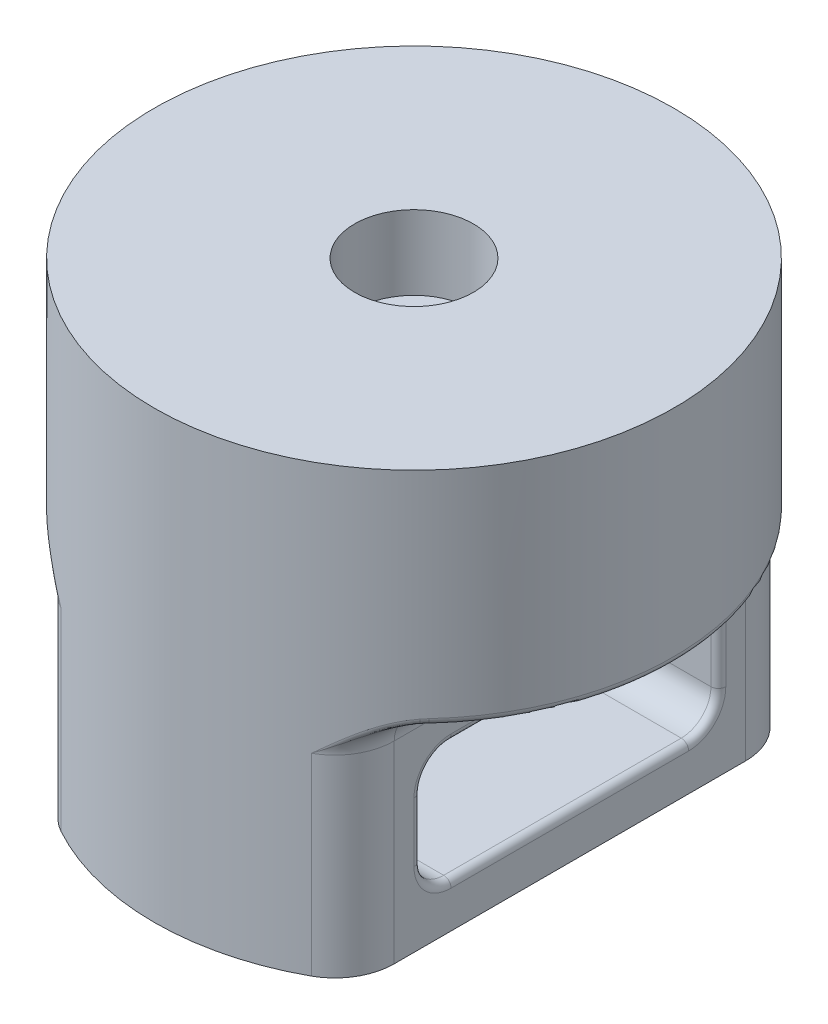
SolidWorks part; units mm, degrees
ref_plane "Front Plane" through (0, 0, 0) normal (0, 0, 1) x (1, 0, 0)
ref_plane "Top Plane" through (0, 0, 0) normal (0, 1, 0) x (1, 0, 0)
ref_plane "Right Plane" through (0, 0, 0) normal (1, 0, 0) x (0, 0, -1)
sketch "Sketch1" plane through (0, 0, 0) normal (0, 1, 0) x (1, 0, 0)
  circle A0 centre (0, 0) radius 17.5
  dimension "D1" = 35
extrude "Boss-Extrude1" add sketch "Sketch1" against normal blind 30
sketch "Sketch2" plane through (0, 0, 0) normal (0, 0, 1) x (1, 0, 0)
  line L0 (-17.5, -15) -> (-10.5, -15)
  line L1 (0, 0) -> (0, -43.743) construction
  line L2 (-10.5, -15) -> (-10.5, -30)
  line L3 (-17.5, -15) -> (-17.5, -30)
  line L4 (-17.5, -30) -> (-10.5, -30)
  line L5 (17.5, -30) -> (10.5, -30)
  line L6 (17.5, -15) -> (17.5, -30)
  line L7 (17.5, -15) -> (10.5, -15)
  line L8 (10.5, -15) -> (10.5, -30)
  dimension "D1" = 7
  dimension "D2" = 15
extrude "Cut-Extrude1" cut sketch "Sketch2" against normal through all both and the other way through all
sketch "Sketch3" plane through (-10.5, 0, 0) normal (-1, 0, 0) x (0, 0, 1)
  line L0 (14, -30) -> (-14, -30) construction
  line L1 (10, -27) -> (-10, -27)
  line L2 (10, -27) -> (10, -19)
  line L3 (10, -19) -> (-10, -19)
  line L4 (-10, -27) -> (-10, -19)
  line L5 (10, -27) -> (-10, -19) construction
  line L6 (10, -19) -> (-10, -27) construction
  point P0 (0, -23)
  dimension "D1" = 20
  dimension "D2" = 8
  dimension "D3" = 3
extrude "Cut-Extrude2" cut sketch "Sketch3" against normal through all both
fillet "Fillet2" radius 2 4 edges at (0, -19, -10) (0, -19, 10) (0, -27, 10) (0, -27, -10)
fillet "Fillet3" radius 4 4 edges at (10.5, -22.5, -14) (10.5, -22.5, 14) (-10.5, -22.5, -14) (-10.5, -22.5, 14)
fillet "Fillet4" radius 2 6 edges at (9.9427, -15, -13.8689) (9.9427, -15, 13.8689) (-9.9427, -15, -13.8689) (-9.9427, -15, 13.8689) (10.5, -15, 0) (-10.5, -15, 0)
fillet "Fillet5" radius 0.5 6 edges at (11.233, -15.2726, -13.419) (17.5, -15, 0) (-11.233, -15.2726, -13.419) (-17.5, -15, 0) (11.233, -15.2726, 13.419) (-11.233, -15.2726, 13.419)
fillet "Fillet6" radius 0.5 16 edges at (-10.5, -19.5858, 9.4142) (-10.5, -23, 10) (-10.5, -26.4142, 9.4142) (-10.5, -27, 0) (-10.5, -26.4142, -9.4142) (-10.5, -23, -10) (-10.5, -19.5858, -9.4142) (10.5, -26.4142, -9.4142) (10.5, -23, -10) (10.5, -19.5858, -9.4142) (10.5, -19, 0) (10.5, -19.5858, 9.4142) (10.5, -23, 10) (10.5, -26.4142, 9.4142) (-10.5, -19, 0) (10.5, -27, 0)
sketch "Sketch6" plane through (0, 0, 0) normal (0, 1, 0) x (1, 0, 0)
  circle A0 centre (0, 0) radius 4
  dimension "D1" = 8
extrude "Cut-Extrude3" cut sketch "Sketch6" against normal blind 5
sketch "Sketch7" plane through (0, -30, 0) normal (0, -1, 0) x (1, 0, 0)
  line L0 (0, 0) -> (-10.5, 0) construction
  line L1 (-10.5, 11.8322) -> (-10.5, -11.8322) construction
  line L2 (0, 0) -> (10.5, 0) construction
  line L3 (10.5, -11.8322) -> (10.5, 11.8322) construction
  line L4 (0, 0) -> (0, -17.5) construction
  line L5 (0, 0) -> (0, 17.5) construction
  line L6 (-7, 0) -> (-7, 12) construction
  line L7 (-7, 12) -> (0, 12) construction
  line L8 (0, 12) -> (7, 12) construction
  line L9 (7, 12) -> (7, 0) construction
  line L10 (7, 0) -> (7, -12) construction
  line L11 (7, -12) -> (0, -12) construction
  line L12 (0, -12) -> (-7, -12) construction
  line L13 (-7, -12) -> (-7, 0) construction
  arc A0 (-8.4259, -15.338) -> (8.4259, -15.338) centre (0, 0) ccw construction
  arc A1 (8.4259, 15.338) -> (-8.4259, 15.338) centre (0, 0) ccw construction
  circle A2 centre (-7, 12) radius 1.25
  circle A3 centre (7, 12) radius 1.25
  circle A4 centre (7, -12) radius 1.25
  circle A5 centre (-7, -12) radius 1.25
  dimension "D3" = 2.5
  dimension "D1" = 12
  dimension "D2" = 7
extrude "Cut-Extrude4" cut sketch "Sketch7" against normal blind 8
chamfer "Chamfer1" distance 1 angle 45 4 edges at (7, -30, -13.25) (-7, -30, -13.25) (-7, -30, 10.75) (7, -30, 10.75)
